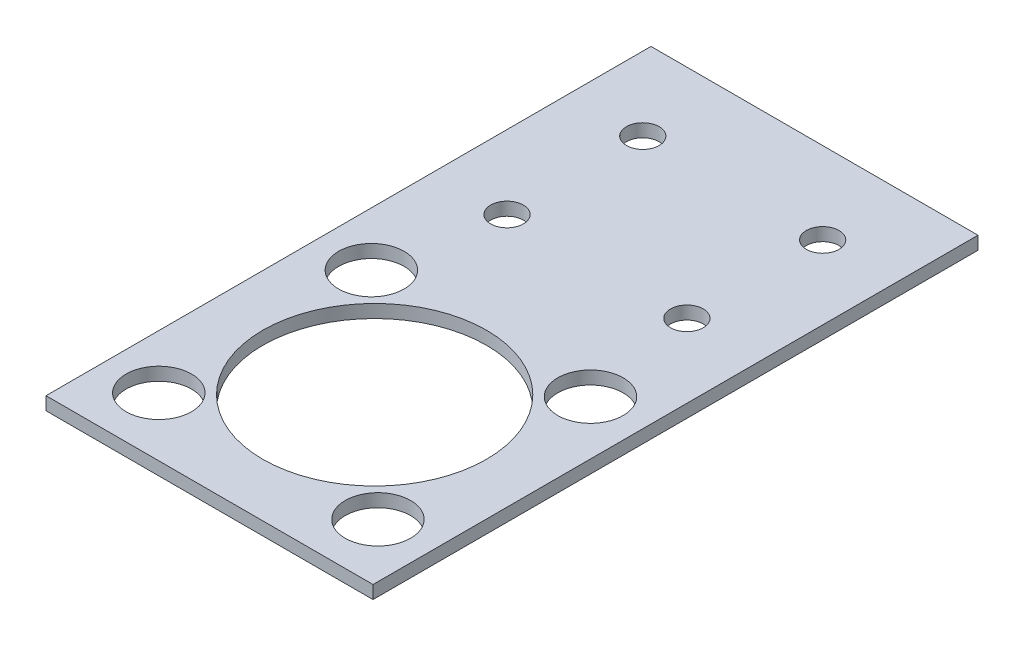
SolidWorks part; units mm, degrees
ref_plane "Front Plane" through (0, 0, 0) normal (0, 0, 1) x (1, 0, 0)
ref_plane "Top Plane" through (0, 0, 0) normal (0, 1, 0) x (1, 0, 0)
ref_plane "Right Plane" through (0, 0, 0) normal (1, 0, 0) x (0, 0, -1)
sketch "Sketch1" plane through (0, 0, 0) normal (0, 1, 0) x (1, 0, 0)
  line L1 (-27.5, 45) -> (22.5, 45)
  line L2 (-27.5, 45) -> (-27.5, -47.5)
  line L3 (-27.5, -47.5) -> (22.5, -47.5)
  line L4 (22.5, 45) -> (22.5, -47.5)
  line L30 (-27.5, 29.49) -> (-27.5, 34.99)
  line L31 (-27.5, 8.99) -> (-27.5, 14.49)
  circle A0 centre (-19.25, -38.5) radius 5
  circle A1 centre (14.25, -38.5) radius 5
  circle A2 centre (14.25, -6) radius 5
  circle A3 centre (-19.25, -6) radius 5
  circle A6 centre (-16.25, 32.5) radius 2.5
  circle A7 centre (-16.25, 11.74) radius 2.5
  circle A8 centre (11.25, 32.5) radius 2.5
  circle A9 centre (11.25, 11.74) radius 2.5
  circle A10 centre (-2.5, -22.25) radius 17.1
  point P0 (0, 0)
  point P6 (0, 0)
  point P8 (0, 0)
  point P10 (-2.8024, -33.1274)
  point P15 (0, 0)
  point P16 (0, 0)
  point P44 (0, 32.24)
  dimension "D15" = 11.25
  dimension "D16" = 11.25
  dimension "D14" = 32.5
  dimension "D17" = 25.25
  dimension "D1" = 50
  dimension "D2" = 92.5
  dimension "D3" = 12.5
  dimension "D4" = 12.5
  dimension "D5" = 11.25
  dimension "D6" = 11.25
  dimension "D7" = 8.25
  dimension "D8" = 8.25
  dimension "D9" = 8.25
  dimension "D10" = 8.25
  dimension "D11" = 32.5
  dimension "D12" = 9
  dimension "D13" = 9
  dimension "D18" = 25
sketch "Sketch2" plane through (0, 0, 0) normal (0, 1, 0) x (1, 0, 0)
  line L1 (-27.5, 45) -> (22.5, 45)
  line L2 (-27.5, 45) -> (-27.5, -47.5)
  line L3 (-27.5, -47.5) -> (22.5, -47.5)
  line L4 (22.5, 45) -> (22.5, -47.5)
base flange "Base-Flange1" sketch "Sketch2" thickness 2 reverse thickness direction no parameters "D1"=0.7366
extrude "Cut-Extrude1" cut sketch "Sketch1" against normal blind 10 contours A7 | A9 | A8 | A0 | A1 | A2 | A3 | A6 | A10
sketch "Bend-Lines1" [suppressed] plane through (0, 0, 0) normal (0, 1, 0) x (1, 0, 0)
sketch "Bounding-Box1" [suppressed] plane through (0, 0, 0) normal (0, 1, 0) x (1, 0, 0)
sheet metal parameters "Sheet-Metal1" thickness 2 parameters "D1"=0.7366
flat pattern "Flat-Pattern1" [suppressed]
sketch "Bend-Lines2" plane through (0, 0, 0) normal (0, 1, 0) x (1, 0, 0)
sketch3d "Bounding-Box2" [suppressed]
  line L0 (22.5, 45, 0) -> (22.5, -45, 0) construction
  line L1 (-22.5, 45, 0) -> (-22.5, -45, 0) construction
  line L2 (22.5, 45, 0) -> (-22.5, 45, 0) construction
  line L3 (22.5, -45, 0) -> (-22.5, -45, 0) construction
sheet metal parameters "Sheet-Metal2" thickness 2 parameters "D1"=0.7366
flat pattern "Flat-Pattern1"
sketch "Bend-Lines2" plane through (0, 0, 0) normal (0, 1, 0) x (1, 0, 0)
sketch3d "Bounding-Box2" [suppressed]
  line L0 (-27.5, 45, 0) -> (-27.5, -47.5, 0) construction
  line L1 (22.5, 45, 0) -> (22.5, -47.5, 0) construction
  line L2 (-27.5, 45, 0) -> (22.5, 45, 0) construction
  line L3 (-27.5, -47.5, 0) -> (22.5, -47.5, 0) construction
